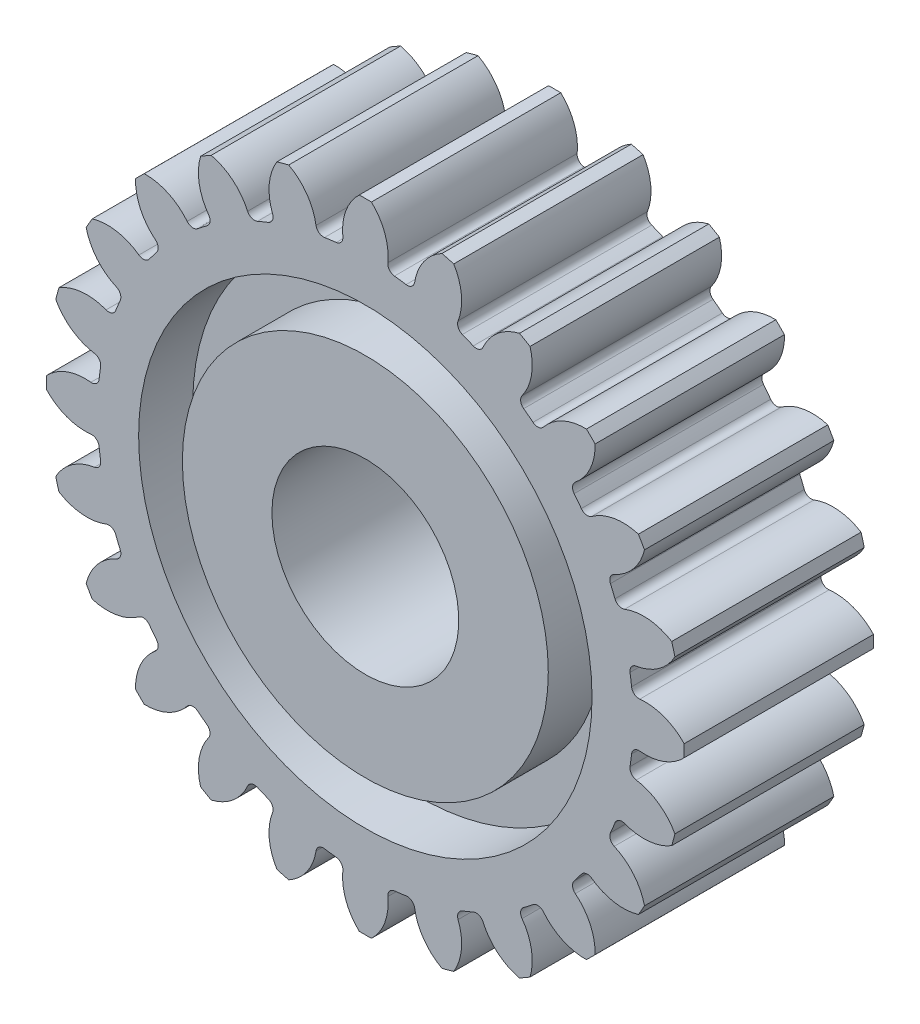
SolidWorks part; units mm, degrees
ref_plane "Front Plane" through (0, 0, 0) normal (0, 0, 1) x (1, 0, 0)
ref_plane "Top Plane" through (0, 0, 0) normal (0, 1, 0) x (1, 0, 0)
ref_plane "Right Plane" through (0, 0, 0) normal (1, 0, 0) x (0, 0, -1)
sketch "Sketch1" plane through (0, 0, 0) normal (1, 0, 0) x (0, 0, -1)
  line L0 (-9.525, 0) -> (-9.525, 16.256)
  line L1 (-9.525, 16.256) -> (0.127, 16.256)
  line L2 (0.127, 16.256) -> (0.127, 9.3269)
  line L3 (0.127, 9.3269) -> (9.525, 9.3269)
  line L4 (9.525, 9.3269) -> (9.525, 0)
  line L5 (9.525, 0) -> (-9.525, 0) construction
  line L6 (-9.525, 4.7625) -> (9.525, 4.7625)
  point P9 (-9.525, 11.557)
  dimension "OD" = 32.512
  dimension "Face Width" = 9.652
  dimension "Hub Width" = 9.398
  dimension "Hub Diameter" = 18.6538
  dimension "For Shaft Diameter" = 9.525
  dimension "Overall Width" = 19.05
  dimension "Under Cut Diameter" = 23.114
sketch "Sketch2" plane through (0, 0, 0) normal (0, 0, 1) x (1, 0, 0)
  line L0 (-1.5975, 13.5587) -> (-0.6158, 16.256)
  line L1 (-0.6158, 16.256) -> (0.6158, 16.256)
  line L2 (0.6158, 16.256) -> (1.5975, 13.5587)
  line L3 (0, 16.256) -> (0, 0) construction
  line L4 (0, 0) -> (-2.1218, 16.1169) construction
  line L5 (0, 0) -> (2.1218, 16.1169) construction
  line L6 (-5.0523, 12.6832) -> (-4.8022, 15.5427)
  line L7 (-4.8022, 15.5427) -> (-3.6126, 15.8615)
  line L8 (-3.6126, 15.8615) -> (-1.9662, 13.5102)
  line L9 (-4.2074, 15.7021) -> (0, 0) construction
  line L11 (-0.6158, 16.256) -> (0, 16.256) construction
  line L12 (-0.9975, 15.2073) -> (0.9975, 15.2073) construction
  circle A0 centre (0, 0) radius 15.24 construction
  circle A2 centre (0, 0) radius 16.256
  circle A3 centre (0, 0) radius 13.6525
  arc A5 (-0.3079, 16.256) -> (-1.0788, 13.6098) centre (1.5607, 14.2762) ccw
  arc A6 (1.0788, 13.6098) -> (0.3079, 16.256) centre (-1.5607, 14.2762) ccw
  arc A7 (-2.4804, 13.4253) -> (-3.91, 15.7818) centre (-5.2025, 13.3858) ccw
  arc A8 (-0.9975, 15.2073) -> (0.9975, 15.2073) centre (0, 0) cw
  point P3 (0, 15.24)
  point P5 (3.9444, 14.7207)
  point P6 (-13.1982, 7.62)
  point P9 (7.62, 13.1982)
  point P10 (10.7763, 10.7763)
  point P11 (13.1982, 7.62)
  point P12 (14.7207, 3.9444)
  point P13 (15.24, 0)
  point P14 (14.7207, -3.9444)
  point P15 (13.1982, -7.62)
  point P16 (10.7763, -10.7763)
  point P17 (7.62, -13.1982)
  point P18 (3.9444, -14.7207)
  point P19 (0, -15.24)
  point P20 (-3.9444, -14.7207)
  point P21 (-7.62, -13.1982)
  point P22 (-10.7763, -10.7763)
  point P23 (-13.1982, -7.62)
  point P24 (-14.7207, -3.9444)
  point P25 (-15.24, 0)
  point P26 (-14.7207, 3.9444)
  point P27 (-10.7763, 10.7763)
  point P28 (-7.62, 13.1982)
  point P29 (-3.9444, 14.7207)
  point P31 (0, 0)
  dimension "Gear Pitch Diameter" = 30.48
  dimension "Pressure Angle" = 20
  dimension "Addendum" = 1.016
  dimension "Dedendum" = 1.5875
  dimension "D1" = 15
  dimension "D2" = 1.9949
  dimension "Number of Teeth" = 24
sketch "Sketch3" plane through (0, 0, 0) normal (1, 0, 0) x (0, 0, -1)
  line L0 (-9.525, 16.256) -> (0.127, 16.256) construction
  line L1 (9.525, 9.3269) -> (9.525, 0) construction
  line L2 (0.127, 9.3269) -> (9.525, 9.3269) construction
  line L3 (0.127, 16.256) -> (0.127, 9.3269) construction
  line L4 (-9.525, 0) -> (-9.525, 16.256) construction
  line L5 (-9.525, 4.7625) -> (9.525, 4.7625) construction
  line L6 (-9.525, 16.256) -> (0.127, 16.256)
  line L7 (9.525, 9.3269) -> (9.525, 4.7625)
  line L8 (-9.525, 9.3269) -> (-6.7673, 9.3269)
  line L9 (0.127, 16.256) -> (0.127, 11.557)
  line L10 (-9.525, 4.7625) -> (-9.525, 9.3269)
  line L11 (-9.525, 4.7625) -> (9.525, 4.7625)
  line L12 (-9.525, 11.557) -> (-6.7673, 11.557)
  line L13 (-6.7673, 11.557) -> (-6.7673, 9.3269)
  line L14 (0.127, 11.557) -> (-2.6307, 11.557)
  line L15 (-2.6307, 11.557) -> (-2.6307, 9.3269)
  line L16 (-2.6307, 9.3269) -> (9.525, 9.3269)
  line L17 (-9.525, 11.557) -> (-9.525, 16.256)
  dimension "D1" = 2.7577
revolve "Revolve1" add sketch "Sketch3" angle 360 about L5
sketch "Sketch4" plane through (0, 0, 9.525) normal (0, 0, 1) x (1, 0, 0)
  arc A1 (-0.3079, 16.256) -> (-1.0788, 13.6098) centre (1.5607, 14.2762) ccw construction
  arc A2 (-2.4804, 13.4253) -> (-3.91, 15.7818) centre (-5.2025, 13.3858) ccw construction
  arc A3 (-0.311, 16.253) -> (-1.1466, 13.9904) centre (1.5607, 14.2762) ccw
  arc A4 (-2.5135, 13.8104) -> (-3.9062, 15.7797) centre (-5.2025, 13.3858) ccw
  circle A5 centre (0, 0) radius 16.256 construction
  arc A6 (-0.311, 16.253) -> (-3.9062, 15.7797) centre (0, 0) ccw
  circle A7 centre (0, 0) radius 13.6525 construction
  arc A8 (-1.4841, 13.5716) -> (-2.0791, 13.4933) centre (0, 0) ccw
  arc A9 (-2.5135, 13.8104) -> (-2.0791, 13.4933) centre (-2.1371, 13.8698) ccw
  arc A10 (-1.4841, 13.5716) -> (-1.1466, 13.9904) centre (-1.5255, 13.9503) ccw
  dimension "D1" = 0.381
extrude "Cut-Extrude1" cut sketch "Sketch4" against normal through all both and the other way through all
pattern_circular "CirPattern1" count 24 over 360 about axis through (0, 0, -9.525) along (0, 0, -1) of "Cut-Extrude1"
sketch "Sketch5" plane through (0, 0, -9.525) normal (0, 0, -1) x (-1, 0, 0)
  circle A1 centre (0, 0) radius 11.557
extrude "Cut-Extrude2" cut sketch "Sketch5" against normal up to surface (9.398 mm away) up to face at (-11.557, 0, -0.127)
equation "\"Dedendum@Sketch2\" = 1.25 /  ( \"Number of Teeth@Sketch2\" / \"Gear Pitch Diameter@Sketch2\" ) "
equation "\"D1@Sketch2\"=360/\"Number of Teeth@Sketch2\""
equation "\"D1@Sketch4\"=.3/(\"Number of Teeth@Sketch2\"/\"Gear Pitch Diameter@Sketch2\")"
equation "\"D1@CirPattern1\"=\"Number of Teeth@Sketch2\""
equation "\"D2@Sketch2\"=1.5708/(\"Number of Teeth@Sketch2\"/\"Gear Pitch Diameter@Sketch2\")"
equation "\"D1@Sketch3\"=\"Face Width@Sketch1\"/3.5"
